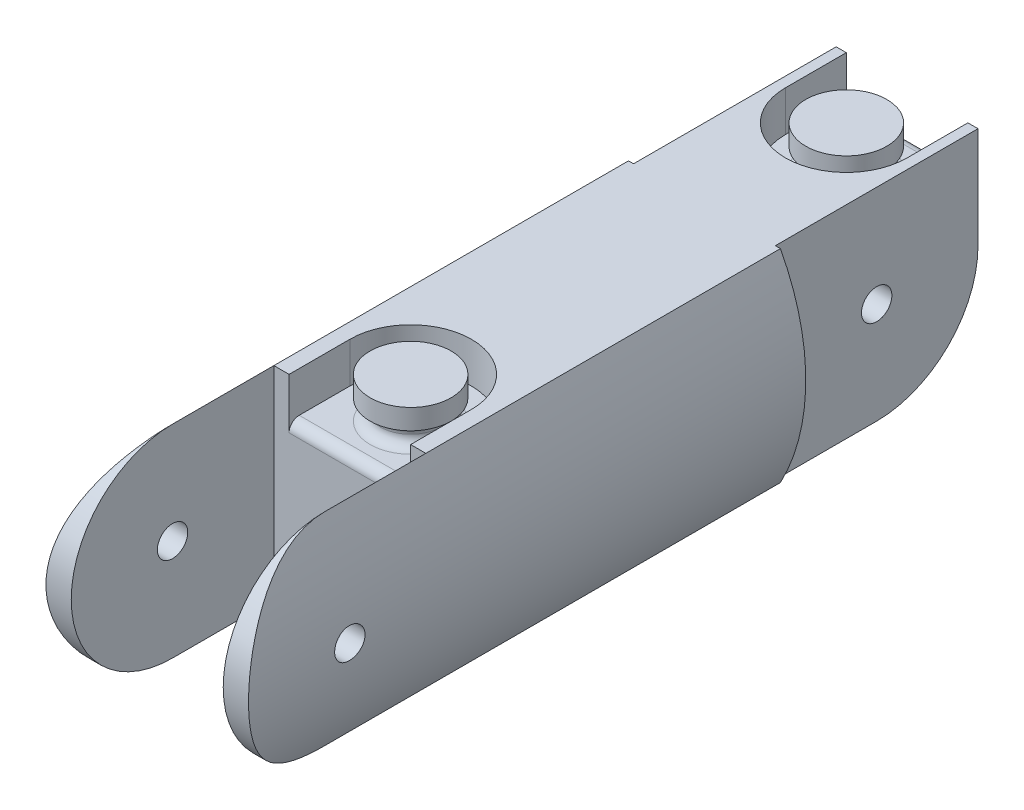
SolidWorks part; units mm, degrees
ref_plane "Alzado" through (0, 0, 0) normal (0, 0, 1) x (1, 0, 0)
ref_plane "Planta" through (0, 0, 0) normal (0, 1, 0) x (1, 0, 0)
ref_plane "Vista lateral" through (0, 0, 0) normal (1, 0, 0) x (0, 0, -1)
sketch "Croquis2" plane through (0, 0, 0) normal (0, 0, 1) x (1, 0, 0)
  line L5 (-7.5, -10) -> (7.5, -10)
  line L7 (-7.5, 10) -> (7.5, 10)
  line L9 (-7.5, -10) -> (7.5, 10) construction
  line L10 (-7.5, 10) -> (7.5, -10) construction
  arc A2 (-7.5, 10) -> (-7.5, -10) centre (11.25, 0) ccw
  arc A3 (7.5, -10) -> (7.5, 10) centre (-11.25, 0) ccw
  point P0 (0, 0)
  dimension "D1" = 15
  dimension "D2" = 20
extrude "Saliente-Extruir2" add sketch "Croquis2" along normal blind 55
sketch "Croquis4" plane through (0, 0, 0) normal (0, 0, -1) x (-1, 0, 0)
  line L1 (7.5, -10) -> (-7.5, -10) construction
  circle A0 centre (0, -7) radius 1.5
  dimension "D2" = 3
  dimension "D1" = 3
extrude "Cortar-Extruir1" cut sketch "Croquis4" against normal blind 50
sketch "Croquis3" plane through (0, 0, 0) normal (0, 0, -1) x (-1, 0, 0)
  line L8 (7.5, -10) -> (-7.5, -10) construction
  line L10 (7, 10) -> (7, -10)
  line L11 (7, -10) -> (3, -10)
  line L12 (-7, 10) -> (-7, -10)
  line L13 (7, 10) -> (-7, -10) construction
  line L14 (7, -10) -> (-7, 10) construction
  line L16 (3, -3) -> (3, -10)
  line L17 (-3, -10) -> (-7, -10)
  line L19 (-3, -3) -> (3, -3)
  line L20 (-3, -3) -> (-3, -10)
  line L21 (-7, 10) -> (7, 10)
  point P0 (0, 0)
  dimension "D1" = 14
  dimension "D2" = 4
  dimension "D3" = 4
  dimension "D4" = 7
extrude "Saliente-Extruir3" add sketch "Croquis3" along normal blind 20
sketch "Croquis8" plane through (-7, 0, 0) normal (-1, 0, 0) x (0, 0, 1)
  line L0 (-20, -10) -> (-20, 10) construction
  line L1 (-20, -10) -> (0, -10) construction
  circle A0 centre (-10, 0) radius 1.5
  point P4 (-20, 0)
  dimension "D1" = 3
  dimension "D2" = 10
  dimension "D3" = 10
extrude "Cortar-Extruir4" cut sketch "Croquis8" against normal blind 14
fillet "Redondeo1" radius 10 2 edges at (-5, -10, -20) (5, -10, -20)
sketch "Croquis6" plane through (0, 0, 55) normal (0, 0, 1) x (1, 0, 0)
  line L1 (-7.5, 10) -> (7.5, 10)
  line L2 (-7.5, 10) -> (-7.5, -10)
  line L3 (-7.5, -10) -> (7.5, -10)
  line L4 (7.5, 10) -> (7.5, -10)
extrude "Cortar-Extruir2" cut sketch "Croquis6" against normal blind 20
sketch "Croquis7" plane through (0, 0, 0) normal (1, 0, 0) x (0, 0, -1)
  line L0 (-55, 10) -> (-55, -10) construction
  line L2 (-45, -10) -> (-60, -10)
  line L4 (-45, 10) -> (-60, 10)
  line L5 (-60, -10) -> (-60, 10)
  arc A0 (-45, 10) -> (-45, -10) centre (-45, 0) ccw
  circle A1 centre (-45, 0) radius 1.5
  dimension "D3" = 10
  dimension "D4" = 3
  dimension "D1" = 10
  dimension "D2" = 15
  dimension "D5" = 20
extrude "Cortar-Extruir3" cut sketch "Croquis7" against normal through all both and the other way through all
sketch "Sketch1" plane through (0, 10, 0) normal (0, 1, 0) x (1, 0, 0)
  line L0 (7.5, -35) -> (-7.5, -35) construction
  line L1 (-7, 20) -> (7, 20) construction
  line L4 (-6, 14) -> (-6, 20)
  line L5 (-6, 20) -> (6, 20)
  line L6 (6, 14) -> (6, 20)
  line L8 (-6, -29) -> (-6, -35)
  line L9 (-6, -35) -> (6, -35)
  line L10 (6, -29) -> (6, -35)
  arc A0 (-6, 14) -> (6, 14) centre (0, 14) ccw
  arc A1 (6, -29) -> (-6, -29) centre (0, -29) ccw
  dimension "D1" = 12
  dimension "D2" = 12
  dimension "D3" = 6
  dimension "D4" = 6
extrude "Cut-Extrude1" cut sketch "Sketch1" against normal blind 4
sketch "Sketch2" plane through (0, 6, 0) normal (0, 1, 0) x (1, 0, 0)
  circle A0 centre (0, -29) radius 3
  circle A1 centre (0, 14) radius 3
  dimension "D1" = 6
  dimension "D2" = 6
extrude "Boss-Extrude1" add sketch "Sketch2" along normal blind 2
sketch "Sketch3" plane through (0, 8, 0) normal (0, 1, 0) x (1, 0, 0)
  circle A0 centre (0, 14) radius 4
  circle A1 centre (0, -29) radius 4
  dimension "D1" = 8
  dimension "D2" = 8
extrude "Boss-Extrude2" add sketch "Sketch3" along normal blind 2
fillet "Fillet1" radius 1 4 edges at (0, 8, -11) (0, 6, -11) (0, 8, 32) (0, 6, 32)
fillet "Fillet2" radius 1 2 edges at (0, 6, 35) (0, 6, -20)
fillet "Fillet3" radius 1 2 edges at (-1.5, -7, 0) (1.5, -7, 35)
